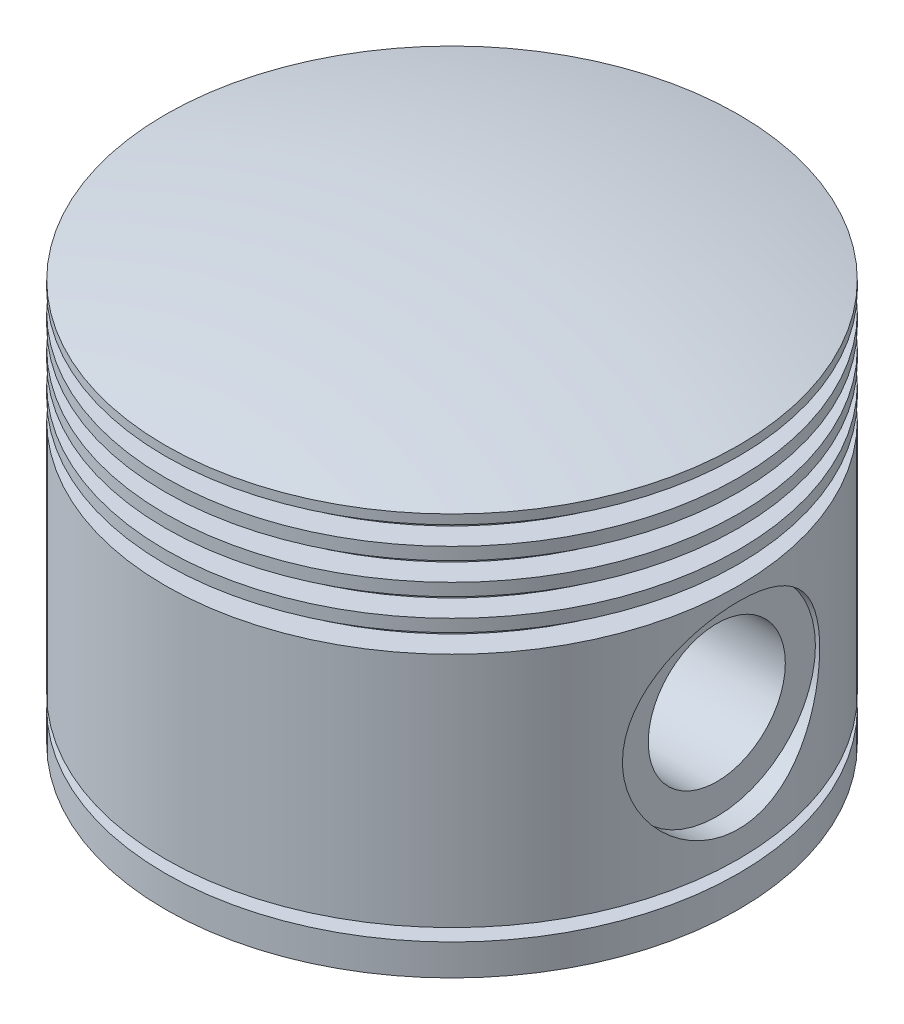
SolidWorks part; units mm, degrees
ref_plane "Front Plane" through (0, 0, 0) normal (0, 0, 1) x (1, 0, 0)
ref_plane "Top Plane" through (0, 0, 0) normal (0, 1, 0) x (1, 0, 0)
ref_plane "Right Plane" through (0, 0, 0) normal (1, 0, 0) x (0, 0, -1)
sketch "Sketch1" plane through (0, 0, 0) normal (0, 0, 1) x (1, 0, 0)
  line L0 (0, 62) -> (0, 3.1644) construction
  line L1 (-49.2126, 0) -> (33.9283, 0) construction
  line L2 (-46, 64.5) -> (-46, 63)
  line L3 (-46, 63) -> (-42, 63)
  line L4 (-42, 63) -> (-42, 60)
  line L5 (-42, 60) -> (-46, 60)
  line L6 (-46, 60) -> (-46, 58)
  line L7 (-46, 58) -> (-42, 58)
  line L8 (-42, 58) -> (-42, 55)
  line L9 (-42, 55) -> (-46, 55)
  line L10 (-46, 55) -> (-46, 53)
  line L11 (-46, 53) -> (-42, 53)
  line L12 (-42, 48) -> (-42, 45)
  line L13 (-42, 53) -> (-42, 50)
  line L14 (-42, 50) -> (-46, 50)
  line L15 (-46, 50) -> (-46, 48)
  line L16 (-42, 48) -> (-42, 45)
  line L19 (-46, 7) -> (-42.5, 7)
  line L20 (-42.5, 7) -> (-42.5, 5)
  line L21 (-42.5, 5) -> (-46, 5)
  line L22 (-46, 5) -> (-46, 0)
  line L23 (-46, 48) -> (-42, 48)
  line L24 (-42, 45) -> (-46, 45)
  line L25 (-46, 5) -> (-46, 0)
  line L26 (-46, 45) -> (-46, 7)
  line L27 (0, 62) -> (-37, 62)
  line L28 (-37, 62) -> (-37, 0)
  line L29 (0, 70.18) -> (0, 62) construction
  line L30 (-46, 0) -> (-37, 0)
  line L31 (0, 70.18) -> (0, 62)
  arc A0 (-46, 64.5) -> (0, 70.18) centre (-0.0133, -118.82) cw
  dimension "D15" = 70.18
  dimension "D18" = 189
  dimension "D1" = 46
  dimension "D2" = 4
  dimension "D3" = 1.5
  dimension "D4" = 3
  dimension "D5" = 2
  dimension "D6" = 62
  dimension "D7" = 3
  dimension "D8" = 2
  dimension "D9" = 3
  dimension "D10" = 2
  dimension "D11" = 2
  dimension "D12" = 3
  dimension "D13" = 42.5
  dimension "D14" = 45
  dimension "D16" = 37
  dimension "D17" = 85
revolve "Revolve1" add sketch "Sketch1" angle 360 about L31 region at (-23.0719, 67.9226, 0)
sketch "Sketch2" plane through (0, 0, 0) normal (1, 0, 0) x (0, 0, -1)
  circle A0 centre (0, 27) radius 11
  dimension "D1" = 22
  dimension "D2" = 27
extrude "Cut-Extrude1" cut sketch "Sketch2" against normal through all and the other way through all
sketch "Sketch3" plane through (0, 0, 0) normal (1, 0, 0) x (0, 0, -1)
  circle A0 centre (0, 27) radius 15.8312
  dimension "D1" = 31.6623
extrude "Cut-Extrude2" cut sketch "Sketch3" against normal blind 3.5 and the other way through all from offset 46
mirror "Mirror1" about plane through (0, 0, 0) normal (1, 0, 0) of "Cut-Extrude2"
sketch "Sketch4" plane through (0, 0, 0) normal (1, 0, 0) x (0, 0, -1)
  circle A1 centre (0, 27) radius 11
  circle A2 centre (-0.893, 27) radius 18
  dimension "D1" = 22
  dimension "D2" = 36
extrude "Boss-Extrude1" add sketch "Sketch4" against normal up to surface (7.8078 mm away) from offset 25 separate body up to face at (-36.9459, 37.8167, -1.9999) offset against normal yes
sketch "Sketch5" plane through (0, 0, 0) normal (1, 0, 0) x (0, 0, -1)
  circle A0 centre (0, 27) radius 11
  circle A1 centre (0, 27) radius 18
  dimension "D1" = 22
  dimension "D2" = 36
extrude "Boss-Extrude4" add sketch "Sketch5" against normal blind 0.5 and the other way blind 12 from offset 25 contours A0 | A1
